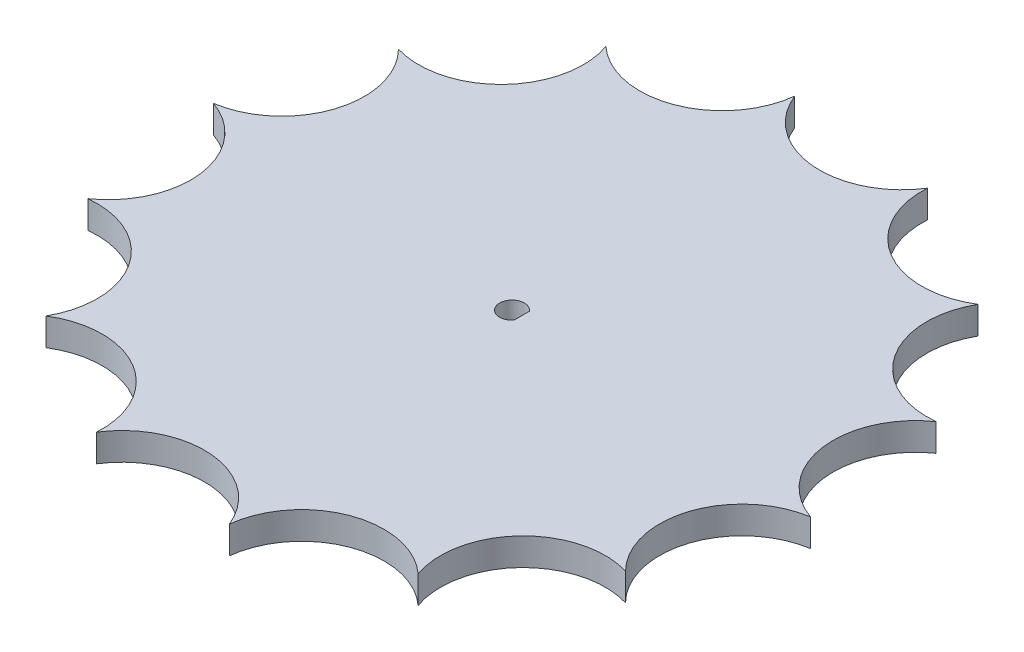
SolidWorks part; units mm, degrees
ref_plane "Front Plane" through (0, 0, 0) normal (0, 0, 1) x (1, 0, 0)
ref_plane "Top Plane" through (0, 0, 0) normal (0, 1, 0) x (1, 0, 0)
ref_plane "Right Plane" through (0, 0, 0) normal (1, 0, 0) x (0, 0, -1)
sketch "Sketch1" plane through (0, 0, 0) normal (0, 1, 0) x (1, 0, 0)
  line L0 (2.237, -1.778) -> (2.237, 1.778)
  arc A0 (2.237, 1.778) -> (2.237, -1.778) centre (0, 0) ccw
  circle A1 centre (0, 0) radius 8.255
  dimension "D1" = 2.8575
  dimension "D3" = 16.51
  dimension "D2" = 3.556
extrude "Boss-Extrude1" add sketch "Sketch1" along normal blind 4.572
sketch "Sketch2" plane through (0, 4.572, 0) normal (0, 1, 0) x (1, 0, 0)
  line L14 (0, 0) -> (-10.1692, 75.5184)
  line L15 (0, 0) -> (23.604, 72.452)
  line L16 (0, 0) -> (52.7022, 55.0356)
  line L17 (0, 0) -> (23.604, 72.452)
  line L18 (0, 0) -> (71.3621, 26.7187)
  line L19 (0, 0) -> (52.7022, 55.0356)
  line L20 (0, 0) -> (75.8879, -6.8901)
  line L21 (0, 0) -> (71.3621, 26.7187)
  line L22 (0, 0) -> (65.3831, -39.1343)
  line L23 (0, 0) -> (75.8879, -6.8901)
  line L24 (0, 0) -> (41.9284, -63.6274)
  line L25 (0, 0) -> (65.3831, -39.1343)
  line L26 (0, 0) -> (10.1692, -75.5184)
  line L27 (0, 0) -> (41.9284, -63.6274)
  line L28 (0, 0) -> (-23.604, -72.452)
  line L29 (0, 0) -> (10.1692, -75.5184)
  line L30 (0, 0) -> (-52.7022, -55.0356)
  line L31 (0, 0) -> (-23.604, -72.452)
  line L32 (0, 0) -> (-71.3621, -26.7187)
  line L33 (0, 0) -> (-52.7022, -55.0356)
  line L34 (0, 0) -> (-75.8879, 6.8901)
  line L35 (0, 0) -> (-71.3621, -26.7187)
  line L36 (0, 0) -> (-65.3831, 39.1343)
  line L37 (0, 0) -> (-75.8879, 6.8901)
  line L38 (0, 0) -> (-41.9284, 63.6274)
  line L39 (0, 0) -> (-65.3831, 39.1343)
  line L40 (0, 0) -> (-10.1692, 75.5184)
  line L41 (0, 0) -> (-41.9284, 63.6274)
  circle A0 centre (0, 0) radius 8.255
  arc A8 (-10.1692, 75.5184) -> (23.604, 72.452) centre (7.5025, 82.6325) ccw
  arc A9 (23.604, 72.452) -> (52.7022, 55.0356) centre (42.6125, 71.1941) ccw
  arc A10 (52.7022, 55.0356) -> (71.3621, 26.7187) centre (69.2825, 45.6548) ccw
  arc A11 (71.3621, 26.7187) -> (75.8879, -6.8901) centre (82.2302, 11.0731) ccw
  arc A12 (75.8879, -6.8901) -> (65.3831, -39.1343) centre (78.8913, -25.7019) ccw
  arc A13 (65.3831, -39.1343) -> (41.9284, -63.6274) centre (59.927, -57.3863) ccw
  arc A14 (41.9284, -63.6274) -> (10.1692, -75.5184) centre (29.0934, -77.7046) ccw
  arc A15 (10.1692, -75.5184) -> (-23.604, -72.452) centre (-7.5025, -82.6325) ccw
  arc A16 (-23.604, -72.452) -> (-52.7022, -55.0356) centre (-42.6125, -71.1941) ccw
  arc A17 (-52.7022, -55.0356) -> (-71.3621, -26.7187) centre (-69.2825, -45.6548) ccw
  arc A18 (-71.3621, -26.7187) -> (-75.8879, 6.8901) centre (-82.2302, -11.0731) ccw
  arc A19 (-75.8879, 6.8901) -> (-65.3831, 39.1343) centre (-78.8913, 25.7019) ccw
  arc A20 (-65.3831, 39.1343) -> (-41.9284, 63.6274) centre (-59.927, 57.3863) ccw
  arc A21 (-41.9284, 63.6274) -> (-10.1692, 75.5184) centre (-29.0934, 77.7046) ccw
  point P27 (0, 0)
  point P49 (0, 0)
  circle M4 centre (0, 0) radius 8.255
  line M5 (2.237, 1.778) -> (2.237, -1.778)
  arc M6 (2.237, -1.778) -> (2.237, 1.778) centre (0, 0) cw
  dimension "D4" = 19.05
  dimension "D1" = 76.2
  dimension "D2" = 25.714
  dimension "D3" = 14
extrude "Boss-Extrude2" add sketch "Sketch2" along normal blind 6.35 contours A16 L28 L30 M4 | A17 L30 L32 M4 | A18 L32 L34 M4 | A19 L34 L36 M4 | A20 L36 L38 M4 | A21 L38 L14 M4 | A8 L14 L15 M4 | A9 L15 L16 M4 | A10 L16 L18 M4 | A11 L18 L20 M4 | A12 L20 L22 M4 | A13 L22 L24 M4 | A14 L24 L26 M4 | A15 L26 L28 M4 | L20 L18 M5 M4 | L18 L16 M5 M4 M6 | L16 L15 M6 M4 | L15 L14 M6 M4 | L38 L14 M6 M4 | L38 L36 M6 M4 | L36 L34 M6 M4 | L34 L32 M6 M4 | L32 L30 M6 M4 | L30 L28 M6 M4 | L28 L26 M6 M4 | L26 L24 M6 M4 | L24 L22 M6 M4 M5 | L22 L20 M5 M4 region at (-2.0839, 4.572, -5.5657) region at (0.5374, 4.572, -5.9187) region at (3.0522, 4.572, -5.0994) region at (4.9198, 4.572, -3.2361) region at (5.7312, 4.572, -0.7709) region at (5.5238, 4.572, 1.7971) region at (4.2852, 4.572, 4.1011) region at (2.0839, 4.572, 5.5657) region at (-0.5374, 4.572, 5.9187) region at (-3.0522, 4.572, 5.0994) region at (-4.9625, 4.572, 3.2701) region at (-5.8899, 4.572, 0.7931) region at (-5.6507, 4.572, -1.8409) region at (-4.2924, 4.572, -4.1104) region at (-15.7868, 4.572, -42.1644) region at (4.071, 4.572, -44.8384) region at (23.1226, 4.572, -38.6317) region at (37.5943, 4.572, -24.7734) region at (44.6201, 4.572, -6.0085) region at (42.8083, 4.572, 13.9465) region at (32.5178, 4.572, 31.1392) region at (15.7868, 4.572, 42.1644) region at (-4.071, 4.572, 44.8384) region at (-23.1226, 4.572, 38.6317) region at (-37.5943, 4.572, 24.7734) region at (-44.6201, 4.572, 6.0085) region at (-42.8083, 4.572, -13.9465) region at (-32.5178, 4.572, -31.1392)
